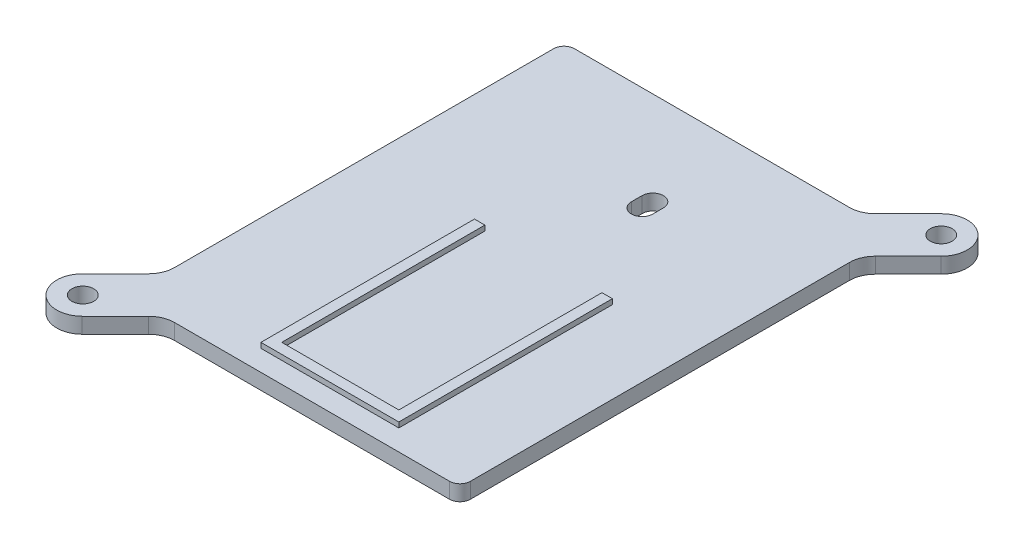
SolidWorks part; units mm, degrees
ref_plane "Front Plane" through (0, 0, 0) normal (0, 0, 1) x (1, 0, 0)
ref_plane "Top Plane" through (0, 0, 0) normal (0, 1, 0) x (1, 0, 0)
ref_plane "Right Plane" through (0, 0, 0) normal (1, 0, 0) x (0, 0, -1)
sketch "Sketch1" plane through (0, 0, 0) normal (0, 1, 0) x (1, 0, 0)
  line L0 (0, 0) -> (0, -84)
  line L1 (0, -84) -> (64, -84)
  line L2 (64, -84) -> (64, 0)
  line L3 (64, 0) -> (0, 0)
  dimension "D1" = 84
  dimension "D2" = 64
extrude "Boss-Extrude1" add sketch "Sketch1" along normal blind 3
sketch "Sketch2" plane through (0, 3, 0) normal (0, 1, 0) x (1, 0, 0)
  line L0 (32, -84) -> (32, 0) construction
  line L1 (0, -84) -> (64, -84) construction
  line L2 (64, 0) -> (0, 0) construction
  line L3 (32, -71.2331) -> (35, -71.2331) construction
  line L4 (35, 0) -> (35, -84) construction
  line L5 (35, -68.9612) -> (46.25, -68.9612) construction
  line L6 (35, -68.9612) -> (23.75, -68.9612) construction
  line L7 (23.75, -68.9612) -> (23.75, -78)
  line L8 (23.75, -78) -> (46.25, -78)
  line L9 (46.25, -68.9612) -> (46.25, -78)
  line L10 (46.25, -68.9612) -> (46.25, -38.9612)
  line L11 (23.75, -68.9612) -> (23.75, -38.9612)
  line L12 (23.75, -38.9612) -> (21.75, -38.9612)
  line L13 (21.75, -38.9612) -> (21.75, -80)
  line L14 (21.75, -80) -> (48.25, -80)
  line L15 (46.25, -38.9612) -> (48.25, -38.9612)
  line L16 (48.25, -38.9612) -> (48.25, -80)
  dimension "D1" = 3
  dimension "D2" = 11.25
  dimension "D3" = 11.25
  dimension "D4" = 6
  dimension "D5" = 30
  dimension "D6" = 30
  dimension "D7" = 2
  dimension "D8" = 2
  dimension "D9" = 2
extrude "Boss-Extrude2" add sketch "Sketch2" along normal blind 1
sketch "Sketch3" plane through (0, 3, 0) normal (0, 1, 0) x (1, 0, 0)
  line L0 (0, -84) -> (-4.2426, -88.2426) construction
  line L1 (64, 0) -> (68.2426, 4.2426) construction
  line L2 (-4.2426, -88.2426) -> (-0.762, -91.8322) construction
  line L3 (-4.2426, -88.2426) -> (-7.7782, -84.7071) construction
  line L4 (-7.7782, -84.7071) -> (0, -76.9289)
  line L5 (0, 0) -> (0, -84) construction
  line L6 (-0.762, -91.8322) -> (7.0702, -84)
  line L7 (0, -84) -> (64, -84) construction
  line L8 (7.0702, -84) -> (0, -76.9289)
  line L9 (-7.7782, -84.7071) -> (-0.7071, -84.7071)
  line L10 (-0.7071, -84.7071) -> (-0.762, -91.8322)
  line L11 (68.2426, 4.2426) -> (71.7782, 0.7071) construction
  line L12 (68.2426, 4.2426) -> (64.7071, 7.7782) construction
  line L13 (71.7782, 0.7071) -> (64, -7.0711)
  line L14 (64, -84) -> (64, 0) construction
  line L15 (64, -7.0711) -> (56.9289, 0)
  line L16 (64, 0) -> (0, 0) construction
  line L17 (56.9289, 0) -> (64.7071, 7.7782)
  line L18 (64.7071, 7.7782) -> (64.7071, 0.7071)
  line L19 (64.7071, 0.7071) -> (71.7782, 0.7071)
  circle A4 centre (-4.2426, -88.2426) radius 2.1
  circle A5 centre (-4.2426, -88.2426) radius 5
  circle A6 centre (68.2426, 4.2426) radius 2.1
  circle A7 centre (68.2426, 4.2426) radius 5
  line M6 (64, 0) -> (0, 0)
  line M7 (0, 0) -> (0, -84)
  line M8 (0, -84) -> (64, -84)
  line M9 (64, -84) -> (64, 0)
  dimension "D2" = 10
  dimension "D3" = 4.2
  dimension "D5" = 10
  dimension "D6" = 4.2
  dimension "D1" = 6
  dimension "D4" = 6
extrude "Boss-Extrude3" add sketch "Sketch3" against normal blind 3 separate body contours A5 L6 L4 M8 M7 | L9 A5 | L6 A5 L10 | L9 A5 L10 A4 | A7 L17 L13 M6 M9 | L19 A7 | L18 A7 | L19 A7 L18 A6 | L8 M8 M7 | L15 M9 M6 region at (-4.2426, 3, 84.1133) region at (-3.7409, 3, 80.9662) region at (-4.2426, 3, 84.8278) region at (2.3567, 3, 81.643) region at (-0.1295, 3, 88.2743) region at (61.643, 3, 2.357) region at (60.9665, 3, -3.7406) region at (70.1099, 3, -8.7505) region at (64.1133, 3, -4.2426) region at (68.2426, 3, -0.1133)
combine bodies "Combine2" operation type add bodies to combine 107 102 108
fillet "Fillet3" radius 5 4 edges at (64, 1.5, 7.0711) (56.9289, 1.5, 0) (0, 1.5, 76.9289) (7.0702, 1.5, 84)
fillet "Fillet4" radius 2 2 edges at (0, 1.5, 0) (64, 1.5, 84)
sketch "Sketch4" plane through (0, 3, 0) normal (0, 1, 0) x (1, 0, 0)
  line L0 (32.95, -17.95) -> (32.95, -20)
  line L1 (37.05, -17.95) -> (37.05, -20)
  arc A0 (32.95, -17.95) -> (37.05, -17.95) centre (35, -17.95) cw
  arc A1 (32.95, -20) -> (37.05, -20) centre (35, -20) ccw
  arc A2 (32.95, -20) -> (37.05, -20) centre (35, -20) ccw construction
extrude "Cut-Extrude1" cut sketch "Sketch4" against normal blind 10
